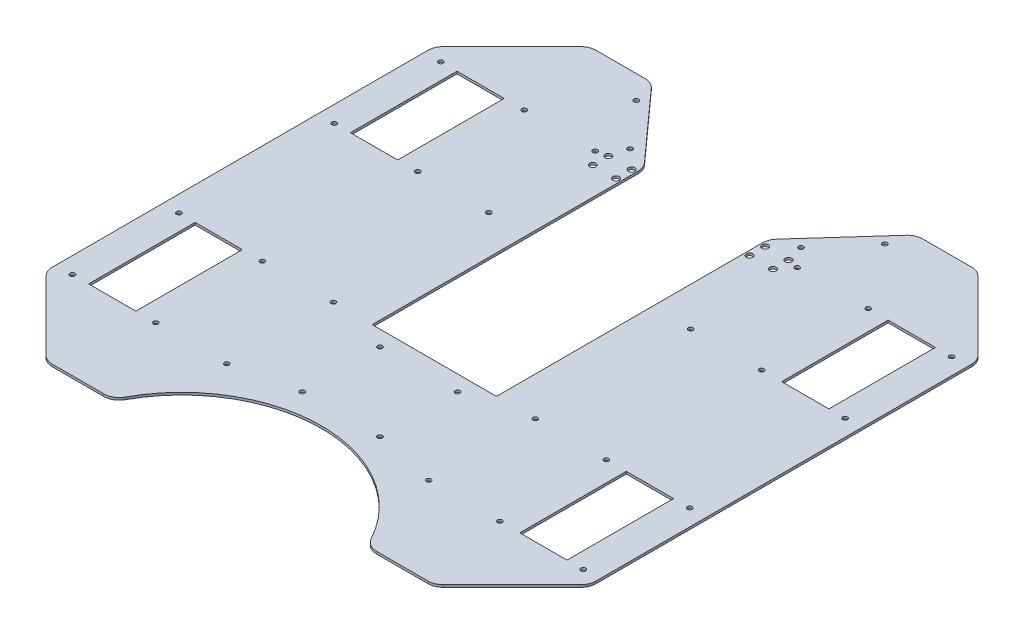
SolidWorks part; units mm, degrees
material "PMMA"
ref_plane "前视基准面" through (0, 0, 0) normal (0, 0, 1) x (1, 0, 0)
ref_plane "上视基准面" through (0, 0, 0) normal (0, 1, 0) x (1, 0, 0)
ref_plane "右视基准面" through (0, 0, 0) normal (1, 0, 0) x (0, 0, -1)
other "Configuration Table"
sketch "草图1" plane through (0, 0, 0) normal (0, 1, 0) x (1, 0, 0)
  line L0 (-125, 175) -> (-175, 125)
  line L1 (125, -175) -> (81.7103, -175)
  line L2 (175, -125) -> (175, 125)
  line L3 (125, 175) -> (85, 175)
  line L4 (-175, -125) -> (-175, 125)
  line L5 (-85, 175) -> (-40, 125)
  line L7 (125, 175) -> (175, 125)
  line L8 (175, -125) -> (125, -175)
  line L9 (-125, -175) -> (-175, -125)
  line L10 (40, 125) -> (85, 175)
  line L11 (-85, 175) -> (-125, 175)
  line L12 (40, 125) -> (40, 85)
  line L13 (40, 85) -> (-40, 85)
  line L14 (-40, 85) -> (-40, 125)
  line L15 (-153.994, 50) -> (-123.594, 50)
  line L16 (-123.594, 50) -> (-123.594, 118.58)
  line L17 (-123.594, 118.58) -> (-153.994, 118.58)
  line L18 (-153.994, 118.58) -> (-153.994, 50)
  line L19 (123.594, 50) -> (153.994, 50)
  line L20 (153.994, 50) -> (153.994, 118.58)
  line L21 (153.994, 118.58) -> (123.594, 118.58)
  line L22 (123.594, 118.58) -> (123.594, 50)
  line L23 (-175, 0) -> (175, 0) construction
  line L24 (-123.594, -118.58) -> (-153.994, -118.58)
  line L25 (-123.594, -50) -> (-123.594, -118.58)
  line L26 (-153.994, -50) -> (-123.594, -50)
  line L27 (-153.994, -118.58) -> (-153.994, -50)
  line L28 (153.994, -118.58) -> (123.594, -118.58)
  line L29 (153.994, -50) -> (153.994, -118.58)
  line L30 (123.594, -50) -> (153.994, -50)
  line L31 (123.594, -118.58) -> (123.594, -50)
  line L32 (-81.7103, -175) -> (-125, -175)
  line L33 (-80, 160) -> (-55, 131) construction
  line L34 (0, 85) -> (0, -124.4881) construction
  line L35 (-40, 85) -> (-40, -25)
  line L36 (-40, -25) -> (40, -25)
  line L37 (40, -25) -> (40, 85)
  circle A0 centre (-55, 131) radius 1.55
  circle A1 centre (-80, 160) radius 1.55
  circle A2 centre (55, 131) radius 1.55
  circle A3 centre (80, 160) radius 1.55
  circle A4 centre (-65, 118.58) radius 1.55
  circle A5 centre (-65, 50) radius 1.55
  circle A6 centre (-110.72, 50) radius 1.55
  circle A7 centre (-110.72, 118.58) radius 1.55
  circle A12 centre (-164.434, 118.58) radius 1.55
  circle A13 centre (-164.434, 50) radius 1.55
  circle A14 centre (-65, -118.58) radius 1.55
  circle A15 centre (-65, -50) radius 1.55
  circle A16 centre (-110.72, -50) radius 1.55
  circle A17 centre (-110.72, -118.58) radius 1.55
  circle A18 centre (-164.434, -50) radius 1.55
  circle A19 centre (-164.434, -118.58) radius 1.55
  circle A20 centre (65, 50) radius 1.55
  circle A21 centre (110.72, 50) radius 1.55
  circle A22 centre (110.72, 118.58) radius 1.55
  circle A23 centre (65, 118.58) radius 1.55
  circle A24 centre (164.434, 118.58) radius 1.55
  circle A25 centre (164.434, 50) radius 1.55
  circle A26 centre (164.434, -118.58) radius 1.55
  circle A27 centre (164.434, -50) radius 1.55
  circle A28 centre (110.72, -50) radius 1.55
  circle A29 centre (110.72, -118.58) radius 1.55
  circle A30 centre (65, -118.58) radius 1.55
  circle A31 centre (65, -50) radius 1.55
  arc A32 (-81.7103, -175) -> (81.7103, -175) centre (0, -212.7283) cw
  circle A33 centre (25, -60) radius 1.55
  circle A34 centre (25, -110) radius 1.55
  circle A35 centre (-25, -60) radius 1.55
  circle A36 centre (-25, -110) radius 1.55
  circle A37 centre (-43, 120) radius 2.05
  circle A38 centre (-43, 110) radius 2.05
  circle A39 centre (-58, 110) radius 2.05
  circle A40 centre (-58, 120) radius 2.05
  circle A41 centre (43, 120) radius 2.05
  circle A42 centre (58, 120) radius 2.05
  circle A43 centre (58, 110) radius 2.05
  circle A44 centre (43, 110) radius 2.05
  point P0 (0, 0)
  point P1 (-85, 175)
  point P2 (85, 175)
  point P3 (40, 125)
  point P4 (-40, 125)
  point P6 (125, 175)
  point P8 (175, 125)
  point P10 (175, -125)
  point P11 (125, -175)
  point P12 (-125, -175)
  point P13 (-175, -125)
  point P24 (-80, 160)
  point P25 (-55, 131)
  point P26 (55, 131)
  point P27 (80, 160)
  point P36 (-164.434, 118.58)
  point P37 (-164.434, 50)
  point P38 (-153.994, 118.58)
  point P39 (-123.594, 50)
  point P40 (-110.72, 118.58)
  point P41 (-110.72, 50)
  point P42 (-65, 118.58)
  point P43 (-65, 50)
  point P47 (-123.594, 118.58)
  point P53 (-153.994, 50)
  point P66 (-40, 85)
  point P67 (40, 85)
  point P70 (110.72, 50)
  point P71 (65, 50)
  point P72 (123.594, 50)
  point P73 (153.994, 50)
  point P74 (164.434, 50)
  point P75 (65, 118.58)
  point P76 (110.72, 118.58)
  point P77 (123.594, 118.58)
  point P78 (153.994, 118.58)
  point P81 (164.434, 118.58)
  point P85 (-65, -118.58)
  point P88 (-65, -50)
  point P91 (-110.72, -50)
  point P94 (-110.72, -118.58)
  point P101 (-164.434, -50)
  point P104 (-164.434, -118.58)
  point P118 (164.434, -118.58)
  point P121 (164.434, -50)
  point P128 (110.72, -50)
  point P131 (110.72, -118.58)
  point P134 (65, -118.58)
  point P137 (65, -50)
  point P157 (58, 110)
  point P158 (43, 110)
  point P159 (43, 120)
  point P160 (58, 120)
  dimension "D29" = 3.1
  dimension "D30" = 3.1
  dimension "D31" = 3.1
  dimension "D32" = 3.1
  dimension "D40" = 3.1
  dimension "D41" = 3.1
  dimension "D42" = 3.1
  dimension "D43" = 3.1
  dimension "D44" = 3.1
  dimension "D45" = 3.1
  dimension "D46" = 3.1
  dimension "D47" = 3.1
  dimension "D48" = 3.1
  dimension "D49" = 3.1
  dimension "D60" = 3.1
  dimension "D61" = 3.1
  dimension "D62" = 43.2897
  dimension "D63" = 90
  dimension "D67" = 3.1
  dimension "D68" = 3.1
  dimension "D69" = 3.1
  dimension "D70" = 3.1
  dimension "D75" = 4.1
  dimension "D76" = 4.1
  dimension "D77" = 4.1
  dimension "D78" = 4.1
  dimension "D80" = 110
  dimension "D1" = 175
  dimension "D2" = 175
  dimension "D3" = 125
  dimension "D4" = 125
  dimension "D5" = 125
  dimension "D6" = 125
  dimension "D7" = 125
  dimension "D8" = 125
  dimension "D9" = 125
  dimension "D10" = 125
  dimension "D11" = 175
  dimension "D12" = 175
  dimension "D13" = 40
  dimension "D14" = 40
  dimension "D15" = 85
  dimension "D16" = 85
  dimension "D17" = 125
  dimension "D18" = 125
  dimension "D19" = 40
  dimension "D20" = 45
  dimension "D21" = 160
  dimension "D22" = 160
  dimension "D23" = 80
  dimension "D24" = 80
  dimension "D25" = 55
  dimension "D26" = 131
  dimension "D27" = 55
  dimension "D28" = 131
  dimension "D33" = 50
  dimension "D34" = 118.58
  dimension "D35" = 65
  dimension "D36" = 45.72
  dimension "D37" = 12.874
  dimension "D38" = 30.4
  dimension "D39" = 10.44
  dimension "D50" = 40
  dimension "D51" = 40
  dimension "D52" = 85
  dimension "D53" = 85
  dimension "D54" = 138.013
  dimension "D55" = 65
  dimension "D56" = 45.72
  dimension "D57" = 12.874
  dimension "D58" = 30.4
  dimension "D59" = 10.44
  dimension "D64" = 0
  dimension "D65" = 25
  dimension "D66" = 25
  dimension "D71" = 60
  dimension "D72" = 50
  dimension "D73" = 15
  dimension "D74" = 10
  dimension "D79" = 43
  dimension "D81" = 120
  dimension "D82" = 110
extrude "凸台-拉伸1" add sketch "草图1" along normal blind 1.5 contours A1 | A0 | L8 L1 A32 L32 L9 L4 L0 L11 L5 L14 L13 L12 L10 L3 L7 L2 | A5 | A3 | A2 | A4 | A7 | A12 | L16 L17 L18 L15 | A6 | L21 L22 L19 L20 | A13 | A16 | A17 | A14 | A15 | A18 | A19 | L25 L24 L27 L26 | A20 | A21 | A22 | A23 | A24 | A25 | A28 | A26 | A27 | L28 L31 L30 L29 | A30 | A31 | A29 | A35 | A36 | A33 | A34 | A39 | A40 | A37 | A38 | A43 | A42 | A41 | A44
fillet "圆角1" radius 10 1 edges at (-40, 0.75, -125)
fillet "圆角2" radius 10 1 edges at (40, 0.75, -125)
fillet "圆角3" radius 10 12 edges at (-85, 0.75, -175) (85, 0.75, -175) (125, 0.75, -175) (175, 0.75, -125) (175, 0.75, 125) (125, 0.75, 175) (81.7103, 0.75, 175) (-81.7103, 0.75, 175) (-125, 0.75, 175) (-175, 0.75, 125) (-175, 0.75, -125) (-125, 0.75, -175)
sketch "草图2" plane through (0, 1.5, 0) normal (0, 1, 0) x (1, 0, 0)
  line L1 (-40, 85) -> (40, 85)
  line L2 (-40, 85) -> (-40, -50)
  line L3 (-40, -50) -> (40, -50)
  line L4 (40, 85) -> (40, -50)
  dimension "D1" = 80
  dimension "D2" = 135
extrude "切除-拉伸1" cut sketch "草图2" against normal blind 10
